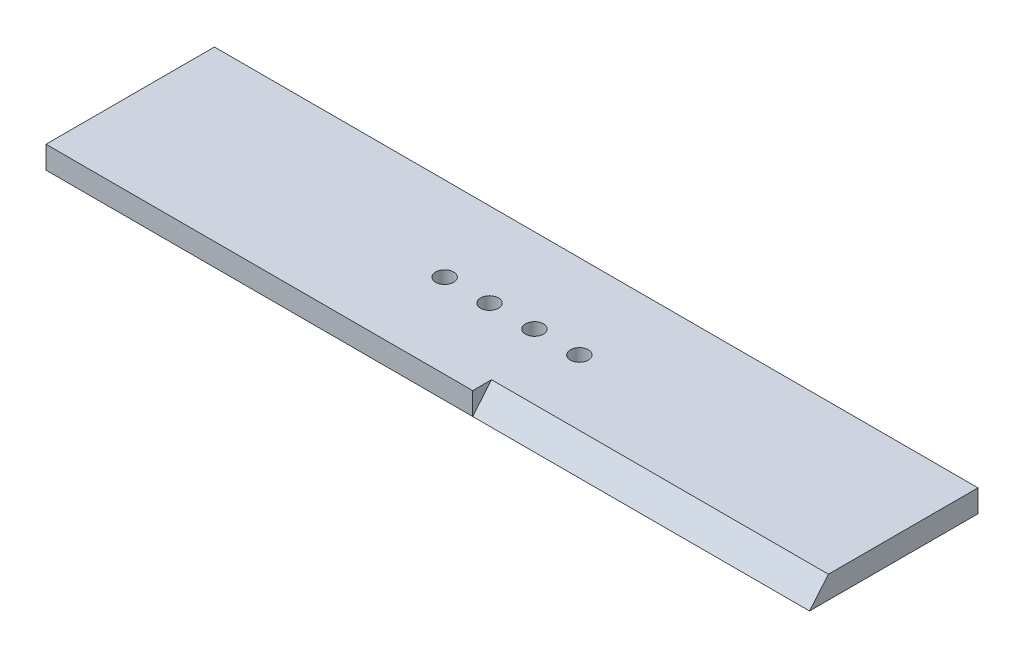
SolidWorks part; units mm, degrees
ref_plane "Front Plane" through (0, 0, 0) normal (0, 0, 1) x (1, 0, 0)
ref_plane "Top Plane" through (0, 0, 0) normal (0, 1, 0) x (1, 0, 0)
ref_plane "Right Plane" through (0, 0, 0) normal (1, 0, 0) x (0, 0, -1)
sketch "Sketch1" plane through (0, 0, 0) normal (0, 1, 0) x (1, 0, 0)
  line L1 (-170, -37.5) -> (170, -37.5)
  line L2 (-170, -37.5) -> (-170, 37.5)
  line L3 (-170, 37.5) -> (170, 37.5)
  line L4 (170, -37.5) -> (170, 37.5)
  line L5 (-170, -37.5) -> (170, 37.5) construction
  line L6 (-170, 37.5) -> (170, -37.5) construction
  point P1 (0, 0)
  dimension "D1" = 340
  dimension "D2" = 75
sketch "Sketch5" plane through (0, 0, 0) normal (0, 1, 0) x (1, 0, 0)
  line L0 (-170, 0) -> (170, 0) construction
  line L1 (-170, -37.5) -> (-170, 37.5) construction
  line L2 (170, -37.5) -> (170, 37.5) construction
  line L3 (0, 37.5) -> (0, -37.5) construction
  line L4 (-170, 37.5) -> (170, 37.5) construction
  line L5 (-170, -37.5) -> (170, -37.5) construction
extrude "Boss-Extrude2" add sketch "Sketch1" along normal mid plane 10
hole_wizard "Ø8.0mm Dowel Hole1" positions "Sketch6" profile "Sketch7" hole size "Ø8.0" standard "ANSI Metric" end condition through all
sketch "Sketch6" plane through (0, 5, 0) normal (0, 1, 0) x (1, 0, 0)
  line L0 (-170, 0) -> (170, 0) construction
  line L1 (-10, 0) -> (10, 0) construction
  line L3 (-30, 0) -> (30, 0) construction
  point P0 (10, 0)
  point P4 (30, 0)
  point P6 (-10, 0)
  point P8 (-30, 0)
  point P15 (0, 0)
  point P25 (0, 0)
  dimension "D1" = 20
  dimension "D2" = 60
sketch "Sketch7" plane through (10, 5, 0) normal (1, 0, 0) x (0, 0, 1)
  line L0 (0, 0) -> (0, 10)
  line L1 (0, 10) -> (4, 10)
  line L2 (4, 10) -> (4, 0)
  line L5 (4, 0) -> (0, 0)
  line L11 (0, -6.35) -> (0, 107.95) construction
  dimension "Thru Hole Dia." = 8
  dimension "Thru Hole Depth" = 10
ref_axis "Axis1" through (0, 0, -46.565) along (0, 0, 1)
ref_axis "Axis2" through (-193.3038, 0, 0) along (1, 0, 0)
ref_point "Point1"
ref_axis "Axis3" through (0, -18.5129, 0) along (0, 1, 0)
ref_plane "Plane1" through (0, 0, 0) normal (0, 1, 0) x (1, 0, 0)
sketch "Sketch10" plane through (170, 0, 0) normal (1, 0, 0) x (0, 0, -1)
  line L0 (-37.5, 5) -> (-37.5, -5)
  line L1 (-37.5, -5) -> (-29.109, 5)
  line L2 (-37.5, 5) -> (37.5, 5) construction
  line L3 (-29.109, 5) -> (-37.5, 5)
  dimension "D1" = 40
extrude "Cut-Extrude3" cut sketch "Sketch10" against normal blind 150
sketch "Sketch11" plane through (-170, 0, 0) normal (-1, 0, 0) x (0, 0, 1)
  line L0 (-37.5, 5) -> (-37.5, -5)
  line L1 (-37.5, -5) -> (-29.109, -5)
  line L2 (-37.5, -5) -> (37.5, -5) construction
  line L3 (-29.109, -5) -> (-37.5, 5)
  dimension "D1" = 40
extrude "Cut-Extrude4" cut sketch "Sketch11" against normal blind 150
